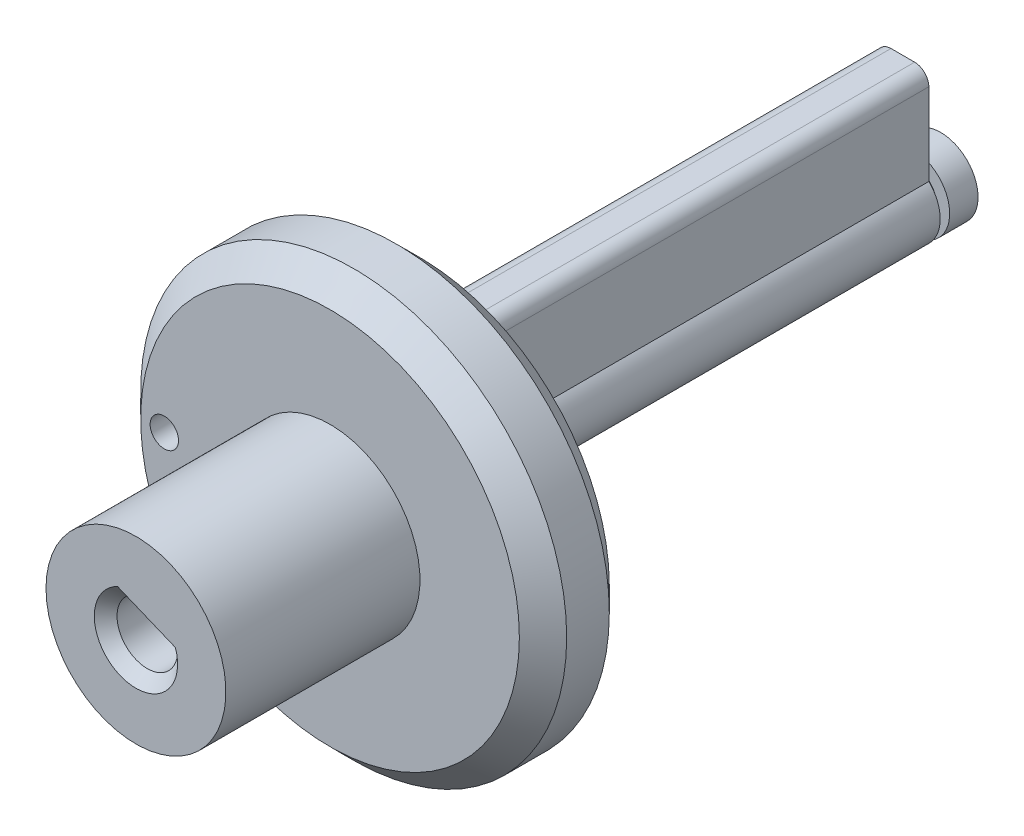
SolidWorks part; units mm, degrees
material "Zinc AG40A (Zn-4Al-0.4Mg; Zamak 3), Cast"
ref_plane "Front Plane" through (0, 0, 0) normal (0, 0, 1) x (1, 0, 0)
ref_plane "Top Plane" through (0, 0, 0) normal (0, 1, 0) x (1, 0, 0)
ref_plane "Right Plane" through (0, 0, 0) normal (1, 0, 0) x (0, 0, -1)
sketch "Sketch1" plane through (0, 0, 0) normal (0, 0, 1) x (1, 0, 0)
  line L0 (-1.2429, 3.556) -> (-1.8135, 0.3198)
  line L1 (-1.2429, 3.556) -> (1.2429, 3.556)
  line L2 (1.2429, 3.556) -> (1.8135, 0.3198)
  line L3 (0, 3.3051) -> (0, 0) construction
  arc A0 (-1.8135, 0.3198) -> (1.8135, 0.3198) centre (0, 0) ccw
  dimension "D1" = 3.683
  dimension "D2" = 10
  dimension "D3" = 10
  dimension "D4" = 3.556
extrude "Extrude1" add sketch "Sketch1" along normal blind 0.0003
sketch "Sketch8" plane through (0, 0, 0.0003) normal (0, 0, 1) x (1, 0, 0)
  circle A2 centre (0, 0) radius 2.413
  dimension "D1" = 4.826
extrude "Extrude8" add sketch "Sketch8" along normal blind 7.62
sketch "Sketch6" plane through (0, 0, 0.0003) normal (0, 0, 1) x (1, 0, 0)
  circle A0 centre (0, 0) radius 5.715
  dimension "D1" = 11.43
extrude "Extrude6" add sketch "Sketch6" along normal blind 2.413
sketch "Sketch4" plane through (0, 0, 7.6203) normal (0, 0, 1) x (1, 0, 0)
  circle A0 centre (0, 0) radius 0.254
  dimension "D1" = 0.508
extrude "Extrude4" cut sketch "Sketch4" against normal blind 6.731
sketch "Sketch5" plane through (0, 0, 0) normal (0, 0, -1) x (-1, 0, 0)
  circle A0 centre (0, 0) radius 1.0033
  dimension "D1" = 2.0066
extrude "Extrude5" add sketch "Sketch5" along normal blind 12.954
fillet "Fillet2" radius 0.889 2 edges at (-1.2429, 3.556, 0.0001) (1.2429, 3.556, 0.0001)
chamfer "Chamfer1" distance 0.635 angle 45 1 edges at (5.715, 0, 0.0003)
chamfer "Chamfer3" distance 0.635 angle 45 1 edges at (5.715, 0, 2.4133)
sketch "Sketch9" plane through (0, 0, 0) normal (0, 0, -1) x (-1, 0, 0)
  line L1 (-0.3175, 3.302) -> (0.3175, 3.302)
  line L2 (-0.6985, 2.921) -> (-0.6985, 0)
  line L3 (-0.6985, 0) -> (0.6985, 0)
  line L4 (0.6985, 2.921) -> (0.6985, 0)
  arc A0 (-0.3175, 3.302) -> (-0.6985, 2.921) centre (-0.3175, 2.921) ccw
  arc A1 (0.3175, 3.302) -> (0.6985, 2.921) centre (0.3175, 2.921) cw
  point P4 (0, 0)
  dimension "D3" = 0.381
  dimension "D1" = 1.397
  dimension "D2" = 3.302
extrude "Extrude9" add sketch "Sketch9" along normal blind 12.954
sketch "Sketch17" plane through (0, 0, 7.6203) normal (0, 0, 1) x (1, 0, 0)
  line L0 (0, 0) -> (0.4411, 1.0649) construction
  line L2 (0, 0) -> (0, 0.8128)
  line L4 (0, 0) -> (0.5747, 0.5747)
  circle A0 centre (0, 0) radius 0.7366 construction
  arc A1 (0.1537, 0.7981) -> (0.4557, 0.673) centre (0.3791, 0.9152) ccw
  arc A3 (0.5747, 0.5747) -> (0.4557, 0.673) centre (0, 0) ccw
  arc A4 (0.1537, 0.7981) -> (0, 0.8128) centre (0, 0) ccw
  dimension "D2" = 45
  dimension "D3" = 22.5
  dimension "D4" = 1.4732
  dimension "D1" = 0.508
  dimension "D6" = 1.6256
extrude "Extrude11" cut sketch "Sketch17" against normal blind 6.731
pattern_circular "CirPattern1" count 8 over 360 about axis through (0, 0, 0) along (0, 0, 1) of "Extrude11"
sketch "Sketch18" plane through (0, 0, 7.6203) normal (0, 0, 1) x (1, 0, 0)
  line L0 (0, 0) -> (-0.3475, 0) construction
  line L1 (-0.5392, 0.6082) -> (0.8113, 0.0488)
  line L2 (-0.5392, 0.6082) -> (-0.3642, 1.0306)
  line L3 (-0.3642, 1.0306) -> (0.9863, 0.4712)
  line L4 (0.8113, 0.0488) -> (0.9863, 0.4712)
  arc A0 (-0.4557, 0.673) -> (-0.673, 0.4557) centre (0, 0) ccw construction
  arc A1 (0.673, 0.4557) -> (0.4557, 0.673) centre (0, 0) ccw construction
  arc A2 (0.7981, -0.1537) -> (0.7981, 0.1537) centre (0, 0) ccw construction
  arc A3 (-0.4599, 0.5754) -> (0.7321, 0.0817) centre (0, 0) cw construction
  arc A4 (0.1537, 0.7981) -> (0.4557, 0.673) centre (0.3791, 0.9152) ccw construction
  dimension "D1" = 0.381
  dimension "D2" = 22.5
extrude "Extrude12" add sketch "Sketch18" against normal up to surface (6.731 mm away) up to face at (0, 0, 0.8893)
chamfer "Chamfer4" distance 0.381 angle 60 1 edges at (0.1361, 0.3285, 7.6203)
sketch "Sketch19" plane through (0, 0, 7.6203) normal (0, 0, 1) x (1, 0, 0)
  line L0 (0.8113, 0.0488) -> (-0.5392, 0.6082) construction
  line L1 (0.8113, 0.0488) -> (-0.5392, 0.6082)
  arc A0 (-0.7981, 0.1537) -> (-0.7981, -0.1537) centre (0, 0) ccw construction
  arc A1 (-0.5392, 0.6082) -> (0.8113, 0.0488) centre (0, 0) ccw
extrude "Extrude13" cut sketch "Sketch19" against normal blind 0.6604
sketch "Sketch20" plane through (0, 0, 0) normal (1, 0, 0) x (0, 0, -1)
  line L0 (-6.9599, -0.8128) -> (-6.9599, 0)
  line L1 (-6.9599, 0) -> (-6.1471, 0)
  line L2 (-6.1471, 0) -> (-6.9599, -0.8128)
  line L5 (-6.9599, -0.6612) -> (-6.9599, -0.7981) construction
  line L6 (-7.3896, 0) -> (-5.2833, 0) construction
  line L7 (-6.9599, -0.673) -> (-6.9599, -0.7981) construction
  dimension "D1" = 0.8128
  dimension "D2" = 45
revolve "Cut-Revolve1" cut sketch "Sketch20" angle 130 about L6
ref_plane "Plane1" through (0, 0, 6.9603) normal (0, 0, 1) x (1, 0, 0)
ref_plane "Plane2" through (0, 0, 6.9603) normal (0, 0, 1) x (1, 0, 0)
sketch "Sketch21" plane through (0, 0, 6.9603) normal (0, 0, 1) x (1, 0, 0)
  line L0 (0.8113, 0.0488) -> (-0.5392, 0.6082) construction
  line L1 (-0.4599, 0.5754) -> (-0.5392, 0.6082)
  line L2 (0.7321, 0.0817) -> (0.8113, 0.0488)
  arc A0 (0.7321, 0.0817) -> (-0.4599, 0.5754) centre (0, 0) cw
  arc A1 (0.8113, 0.0488) -> (-0.5392, 0.6082) centre (0, 0) cw
  arc A2 (-0.0356, 0.812) -> (0.5993, 0.549) centre (0, 0) ccw construction
  dimension "D1" = 0.7366
extrude "Boss-Extrude1" add sketch "Sketch21" against normal up to surface (6.0711 mm away) up to face at (-0.0964, -0.2328, 0.8893)
sketch "Sketch22" plane through (0, 0, 6.9603) normal (0, 0, 1) x (1, 0, 0)
  line L2 (-0.4599, 0.5754) -> (-0.5392, 0.6082)
  line L3 (0.8113, 0.0488) -> (0.7321, 0.0817)
  line L4 (-0.4599, 0.5754) -> (-0.5392, 0.6082)
  line L5 (0.8113, 0.0488) -> (0.7321, 0.0817)
  arc A2 (-0.4599, 0.5754) -> (0.7321, 0.0817) centre (0, 0) ccw
  arc A3 (-0.5392, 0.6082) -> (0.8113, 0.0488) centre (0, 0) ccw
  arc A4 (-0.4599, 0.5754) -> (0.7321, 0.0817) centre (0, 0) ccw
  arc A5 (-0.5392, 0.6082) -> (0.8113, 0.0488) centre (0, 0) ccw
  dimension "D1" = 0
extrude "Cut-Extrude1" cut sketch "Sketch22" against normal offset from surface (0.8387 mm away) 1.4986 up to face at (-0.0146, -0.0352, 7.6203)
chamfer "Chamfer5" distance 0.1016 angle 45 1 edges at (-0.2819, -0.6805, 6.1217)
chamfer "Chamfer6" distance 0.3048 angle 45 1 edges at (-0.311, -0.7509, 7.6203)
sketch "Sketch27" plane through (0, 0, 0) normal (0, 0, 1) x (1, 0, 0)
  circle A0 centre (-4.445, 0) radius 0.381
extrude "Cut-Extrude5" cut sketch "Sketch27" along normal through all
sketch "Sketch28" plane through (0, 0, 0.0003) normal (0, 0, -1) x (-1, 0, 0)
  line L0 (4.445, 1.0147) -> (6.1908, 1.4132)
  line L1 (4.445, -1.0147) -> (6.1908, -1.4132)
  arc A0 (4.445, 1.0147) -> (4.445, -1.0147) centre (4.445, 0) ccw
  arc A3 (6.1908, -1.4132) -> (6.1908, 1.4132) centre (0, 0) ccw
extrude "Cut-Extrude7" cut sketch "Sketch28" against normal blind 1.27 contours L0 A3 L1 A0
sketch "Sketch29" plane through (0, 0, -12.954) normal (0, 0, -1) x (-1, 0, 0)
  circle A0 centre (0, 0) radius 0.6604
extrude "Boss-Extrude2" add sketch "Sketch29" along normal blind 1.016
sketch "Sketch30" plane through (0, 0, -13.97) normal (0, 0, -1) x (-1, 0, 0)
  circle A0 centre (0, 0) radius 1.0033
extrude "Boss-Extrude3" add sketch "Sketch30" against normal blind 0.762
